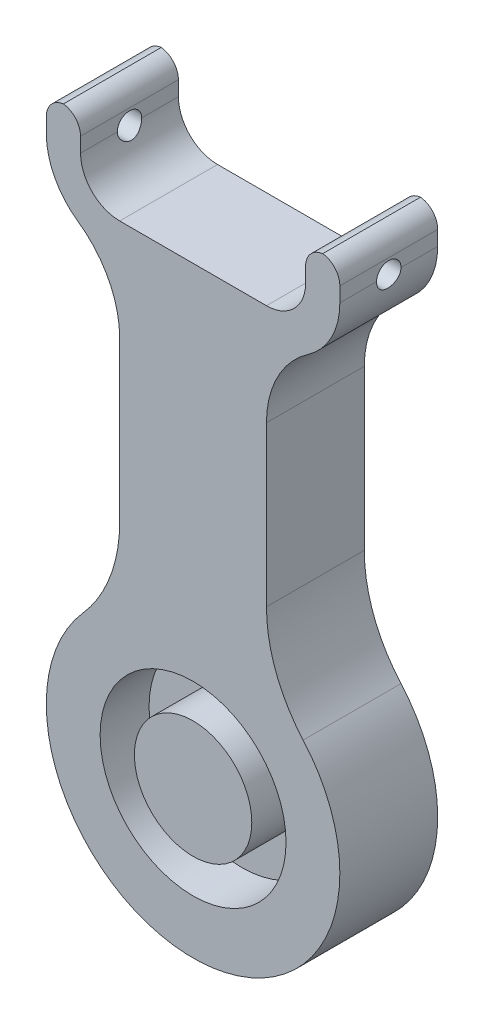
SolidWorks part; units mm, degrees
ref_plane "Front Plane" through (0, 0, 0) normal (0, 0, 1) x (1, 0, 0)
ref_plane "Top Plane" through (0, 0, 0) normal (0, 1, 0) x (1, 0, 0)
ref_plane "Right Plane" through (0, 0, 0) normal (1, 0, 0) x (0, 0, -1)
sketch "Sketch1" plane through (0, 0, 0) normal (0, 0, 1) x (1, 0, 0)
  circle A0 centre (0, 0) radius 15
  circle A1 centre (0, 0) radius 3
  dimension "D1" = 6
  dimension "D2" = 30
extrude "Boss-Extrude1" add sketch "Sketch1" along normal blind 10
sketch "Sketch2" plane through (0, 0, 0) normal (0, 0, 1) x (1, 0, 0)
  line L1 (-7.5, 12.9904) -> (7.5, 12.9904)
  line L2 (-7.5, 12.9904) -> (-7.5, 42.9904)
  line L3 (-7.5, 42.9904) -> (7.5, 42.9904)
  line L4 (7.5, 12.9904) -> (7.5, 42.9904)
  circle A0 centre (0, 0) radius 15 construction
  dimension "D1" = 15
  dimension "D2" = 30
extrude "Boss-Extrude2" add sketch "Sketch2" along normal up to surface (10 mm away) up to face at (15, 0, 10)
fillet "Fillet1" radius 15 2 edges at (-7.5, 12.9904, 5) (7.5, 12.9904, 5)
sketch "Sketch5" plane through (0, 0, 0) normal (0, 0, -1) x (-1, 0, 0)
  line L1 (-5, 3.5) -> (5, 3.5)
  line L2 (-5, 3.5) -> (-5, 1.5)
  line L3 (-5, 1.5) -> (5, 1.5)
  line L4 (5, 3.5) -> (5, 1.5)
  circle A0 centre (0, 0) radius 3 construction
  dimension "D1" = 1.5
  dimension "D2" = 2
  dimension "D3" = 10
  dimension "D4" = 5
extrude "Boss-Extrude3" add sketch "Sketch5" against normal blind 10
sketch "Sketch7" plane through (0, 0, 10) normal (0, 0, 1) x (1, 0, 0)
  circle A0 centre (0, 0) radius 3
extrude "Boss-Extrude4" add sketch "Sketch7" against normal blind 3
chamfer "Chamfer1" distance 0.7 angle 45 2 edges at (0, -3, 7) (0, 1.5, 7)
sketch "Sketch9" plane through (0, 0, 0) normal (0, 0, -1) x (-1, 0, 0)
  line L0 (-7.5, 42.9904) -> (7.5, 42.9904) construction
  line L1 (-7.5, 19.8431) -> (-7.5, 42.9904) construction
  line L3 (-15, 50.4904) -> (-15, 53.9904)
  line L4 (-15, 53.9904) -> (-11.5, 53.9904)
  line L5 (-11.5, 53.9904) -> (-11.5, 50.4904)
  line L6 (-7.5, 46.4904) -> (7.5, 46.4904)
  line L7 (0, 46.4904) -> (0, 42.9904)
  line L8 (7.5, 42.9904) -> (-7.5, 42.9904)
  line L9 (0, 62.4917) -> (0, 38.0275) construction
  line L10 (11.5, 53.9904) -> (11.5, 50.4904)
  line L11 (15, 53.9904) -> (11.5, 53.9904)
  line L12 (15, 50.4904) -> (15, 53.9904)
  arc A0 (-15, 50.4904) -> (-7.5, 42.9904) centre (-7.5, 50.4904) ccw
  arc A2 (-11.5, 50.4904) -> (-7.5, 46.4904) centre (-7.5, 50.4904) ccw
  arc A3 (11.5, 50.4904) -> (7.5, 46.4904) centre (7.5, 50.4904) cw
  arc A4 (15, 50.4904) -> (7.5, 42.9904) centre (7.5, 50.4904) cw
  line M23 (7.5, 42.9904) -> (-7.5, 42.9904)
  dimension "D1" = 3.5
  dimension "12.5" = 15
  dimension "D2" = 7.5
  dimension "D3" = 0
  dimension "D7" = 3.5
  dimension "D8" = 0
extrude "Boss-Extrude6" add sketch "Sketch9" against normal blind 10 contours A2 L5 L4 L3 A0 L7 L6 M23 | A4 L12 L11 L10 A3 L6 L7 M23 region at (14.814, 52.2404, 0) region at (-0.186, 44.7404, 0)
fillet "Fillet4" radius 2 4 edges at (11.5, 53.9904, 5) (15, 53.9904, 5) (-11.5, 53.9904, 5) (-15, 53.9904, 5)
fillet "Fillet2" radius 10 2 edges at (-7.5, 42.9904, 5) (7.5, 42.9904, 5)
sketch "Sketch10" plane through (15, 0, 0) normal (1, 0, 0) x (0, 0, -1)
  line L0 (-10, 50.4904) -> (0, 50.4904) construction
  line L1 (0, 44.3355) -> (0, 50.4904) construction
  circle A0 centre (-5, 50.4904) radius 1.25
  dimension "D3" = 2.5
  dimension "D1" = 0
  dimension "D2" = 5
extrude "Cut-Extrude1" cut sketch "Sketch10" against normal through all both and the other way through all
sketch "Sketch11" plane through (0, 0, 10) normal (0, 0, 1) x (1, 0, 0)
  circle A0 centre (0, 0) radius 9.5
  circle A1 centre (0, 0) radius 6
  point P5 (0, -0.6621)
  dimension "D1" = 19
  dimension "D2" = 12
extrude "Cut-Extrude2" cut sketch "Sketch11" against normal blind 5
